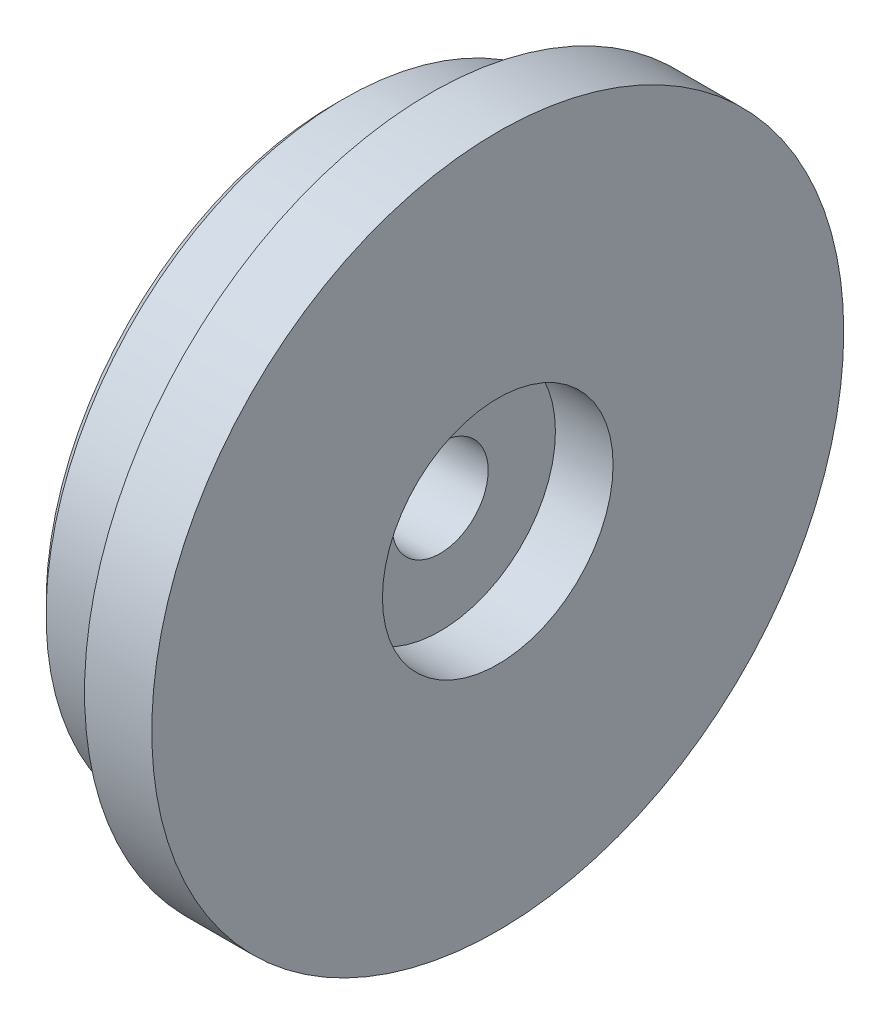
SolidWorks part; units mm, degrees
material "Alliage de zinc AC41A, brut"
ref_plane "Plan de face" through (0, 0, 0) normal (0, 0, 1) x (1, 0, 0)
ref_plane "Plan de dessus" through (0, 0, 0) normal (0, 1, 0) x (1, 0, 0)
ref_plane "Plan de droite" through (0, 0, 0) normal (1, 0, 0) x (0, 0, -1)
sketch "Esquisse1" plane through (0, 0, 0) normal (0, 0, 1) x (1, 0, 0)
  line L0 (0, 0) -> (0, 18) construction
  line L1 (0, 18) -> (-3.5, 18)
  line L2 (0, 18) -> (0, 6)
  line L3 (-3.5, 18) -> (-3.5, 15)
  line L4 (-3.5, 15) -> (-4.5, 15)
  line L5 (-4.5, 15) -> (-4.5, 15.5)
  line L6 (-4.5, 15.5) -> (-8, 15.5)
  line L8 (0, 6) -> (-3, 6)
  line L9 (-3, 6) -> (-3, 2.5)
  line L10 (-3, 2.5) -> (-8.5, 2.5)
  line L11 (-8, 15.5) -> (-8.5, 15)
  line L12 (-8.5, 2.5) -> (-8.5, 5)
  line L13 (-8.5, 5) -> (-5.75, 5)
  line L14 (-5, 5.75) -> (-5, 11.25)
  line L15 (-5.75, 12) -> (-8.5, 12)
  line L16 (-8.5, 12) -> (-8.5, 15)
  line L17 (-5, 11.25) -> (-5.75, 12)
  line L18 (-5.75, 5) -> (-5, 5.75)
  line L19 (0, 0) -> (-8.5, 0) construction
  line L20 (0, 0) -> (0, 6) construction
  point P8 (-8.5, 15.5)
  point P13 (-5, 5)
  point P15 (-5, 12)
  dimension "D2" = 3.5
  dimension "D3" = 12
  dimension "D4" = 3
  dimension "D5" = 1
  dimension "D6" = 0.5
  dimension "D7" = 2.75
  dimension "D8" = 2.5
  dimension "D9" = 3
  dimension "D10" = 3.5
  dimension "D11" = 5.5
  dimension "D12" = 3.5
  dimension "D13" = 0.5
  dimension "D14" = 7
  dimension "D15" = 3
  dimension "D17" = 0.75
  dimension "D20" = 0.75
  dimension "D18" = 0.75
  dimension "D16" = 3.5
  dimension "D21" = 0.75
revolve "Révolution1789" add sketch "Esquisse1" angle 360 about L19
cosmetic thread "Représentation de filetage1"
cosmetic thread "Représentation de filetage2"
